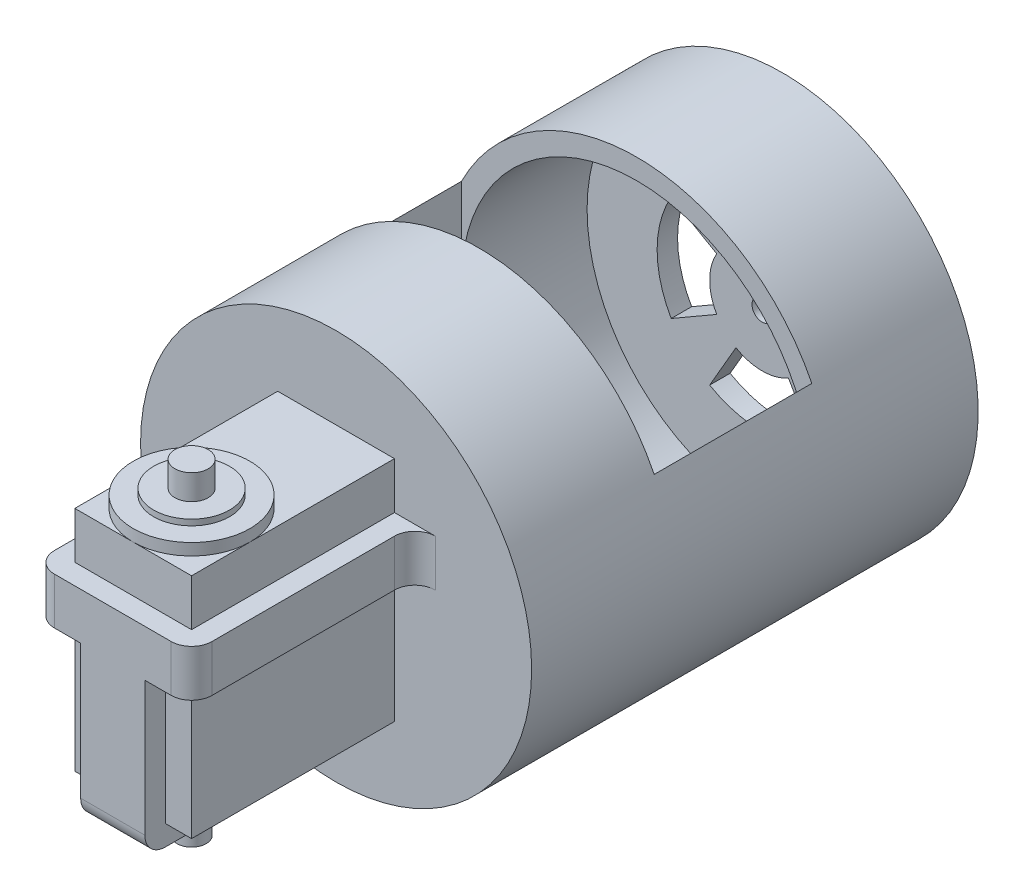
SolidWorks part; units mm, degrees
ref_plane "Front Plane" through (0, 0, 0) normal (0, 0, 1) x (1, 0, 0)
ref_plane "Top Plane" through (0, 0, 0) normal (0, 1, 0) x (1, 0, 0)
ref_plane "Right Plane" through (0, 0, 0) normal (1, 0, 0) x (0, 0, -1)
sketch "Sketch1" plane through (0, 0, 0) normal (0, 0, 1) x (1, 0, 0)
  circle A1 centre (0, 0) radius 33.5
extrude "Boss-Extrude3" add sketch "Sketch1" along normal blind 16.5 contours A1
sketch "Sketch2" plane through (0, 0, 16.5) normal (0, 0, 1) x (1, 0, 0)
  line L0 (0, 0) -> (33.5, 0) construction
  line L1 (-10, 19.5) -> (10, 19.5)
  line L2 (-10, 19.5) -> (-10, -19.5)
  line L3 (-10, -19.5) -> (10, -19.5)
  line L4 (10, 19.5) -> (10, -19.5)
  line L5 (0, 0) -> (0, -33.5) construction
  circle A0 centre (0, 0) radius 33.5 construction
  dimension "D1" = 10
  dimension "D2" = 19.5
extrude "Boss-Extrude4" add sketch "Sketch2" along normal blind 34.758
sketch "Sketch3" plane through (0, 19.5, 0) normal (0, 1, 0) x (1, 0, 0)
  circle A0 centre (0, -41.258) radius 10
  circle A1 centre (0, -41.258) radius 6.5
  circle A2 centre (0, -41.258) radius 2.85
extrude "Boss-Extrude5" add sketch "Sketch3" along normal blind 2 contours A0 A1 region at (-9.7172, 19.5, 41.258)
extrude "Boss-Extrude6" add sketch "Sketch3<3>" along normal blind 3 contours A1
sketch "Sketch3<3>" plane through (0, 19.5, 0) normal (0, 1, 0) x (1, 0, 0) same geometry as "Sketch3"
extrude "Boss-Extrude7" add sketch "Sketch3<4>" along normal blind 7.3 contours A2
sketch "Sketch3<4>" plane through (0, 19.5, 0) normal (0, 1, 0) x (1, 0, 0) same geometry as "Sketch3"
sketch "Sketch5" plane through (0, 0, 51.258) normal (0, 0, 1) x (1, 0, 0)
  line L0 (-10, -19.5) -> (10, -19.5) construction
  line L1 (-5.5, -23) -> (5.5, -23)
  line L2 (-5.5, -23) -> (-5.5, -19.5)
  line L3 (-5.5, -19.5) -> (5.5, -19.5)
  line L4 (5.5, -23) -> (5.5, -19.5)
  line L5 (10, -19.5) -> (10, 19.5) construction
  line L6 (10, 11.5) -> (13.5, 11.5)
  line L7 (10, 11.5) -> (10, 3.5)
  line L8 (10, 3.5) -> (13.5, 3.5)
  line L9 (13.5, 11.5) -> (13.5, 3.5)
  line L10 (-10, 19.5) -> (-10, -19.5) construction
  line L11 (-10, 11.5) -> (-13.5, 11.5)
  line L12 (-10, 11.5) -> (-10, 3.5)
  line L13 (-10, 3.5) -> (-13.5, 3.5)
  line L14 (-13.5, 11.5) -> (-13.5, 3.5)
  line L15 (-10, -19.5) -> (10, -19.5) construction
  point P19 (0, 0)
  point P20 (0, 0)
  point P21 (-11.75, 3.5)
  dimension "D1" = 5.5
  dimension "D2" = 23
  dimension "D3" = 23
  dimension "D4" = 8
  dimension "D5" = 8
  dimension "D6" = 3.5
  dimension "D7" = 3.5
extrude "Boss-Extrude8" add sketch "Sketch5" against normal up to surface (34.758 mm away) up to face at (0, 0, 16.5)
sketch "Sketch6" plane through (0, 0, 51.258) normal (0, 0, 1) x (1, 0, 0)
  line L1 (-13.5, 11.5) -> (13.5, 11.5)
  line L2 (-13.5, 11.5) -> (-13.5, 3.5)
  line L3 (-13.5, 3.5) -> (13.5, 3.5)
  line L4 (13.5, 11.5) -> (13.5, 3.5)
  line L5 (5.5, -23) -> (-5.5, -23)
  line L6 (5.5, -23) -> (5.5, 11.5)
  line L7 (5.5, 11.5) -> (-5.5, 11.5)
  line L8 (-5.5, -23) -> (-5.5, 11.5)
  point P11 (-5.5, -23)
  line M6 (-10, 11.5) -> (-13.5, 11.5)
  line M7 (-13.5, 11.5) -> (-13.5, 3.5)
  line M8 (-13.5, 3.5) -> (-10, 3.5)
  line M11 (-5.5, -19.5) -> (-5.5, -23)
  line M12 (-5.5, -23) -> (5.5, -23)
  line M13 (5.5, -23) -> (5.5, -19.5)
  line M16 (10, 3.5) -> (13.5, 3.5)
  line M17 (13.5, 3.5) -> (13.5, 11.5)
  line M18 (13.5, 11.5) -> (10, 11.5)
extrude "Boss-Extrude9" add sketch "Sketch6" along normal blind 3.5 contours L8 L3 L6 L1 | L6 L3 L1 M16 M17 M18 | L8 L6 L3 M11 M12 M13 | L3 L8 L1 M6 M7 M8 region at (-9.5, 7.5, 51.258) region at (0, 7.5, 51.258) region at (9.5, 7.5, 51.258) region at (0, -9.75, 51.258)
sketch "Sketch7" plane through (0, -23, 0) normal (0, -1, 0) x (1, 0, 0)
  circle A0 centre (0, 41.258) radius 2.5
extrude "Boss-Extrude10" add sketch "Sketch7" along normal blind 6 contours A0
fillet "Fillet1" radius 3.5 2 edges at (-13.5, 7.5, 54.758) (13.5, 7.5, 54.758)
fillet "Fillet2" radius 3.5 1 edges at (0, -23, 54.758)
fillet "Fillet3" radius 3.5 1 edges at (13.5, 7.5, 16.5)
fillet "Fillet4" radius 3.5 1 edges at (-13.5, 7.5, 16.5)
sketch "Sketch14" plane through (0, 0, 0) normal (0, 0, -1) x (-1, 0, 0)
  line L0 (0, 0) -> (0, 18) construction
  line L1 (0, 0) -> (9, 15.5885)
  line L2 (0, 0) -> (-9, 15.5885)
  circle A0 centre (0, 0) radius 1.25
  circle A1 centre (0, 0) radius 9
  circle A2 centre (0, 0) radius 18
  dimension "D1" = 60
  dimension "D2" = 30
extrude "Cut-Extrude11" cut sketch "Sketch14" against normal blind 3.5 contours L0 A1 L1 A2 | A1 L0 A2 L2 region at (3.5822, 13.369, 0) region at (-3.5822, 13.369, 0)
pattern_circular "CirPattern4" count 4 over 360 about axis through (0, 0, 0) along (0, 0, 1) of "Cut-Extrude11"
extrude "Cut-Extrude12" cut sketch "Sketch14<3>" against normal blind 3.5 contours A0
sketch "Sketch14<3>" plane through (0, 0, 0) normal (0, 0, -1) x (-1, 0, 0) same geometry as "Sketch14"
sketch "Sketch16" plane through (0, 0, 0) normal (0, 0, -1) x (-1, 0, 0)
  circle A0 centre (0, 0) radius 33.5
  circle A1 centre (0, 0) radius 30
extrude "Boss-Extrude15" add sketch "Sketch16" along normal blind 60 contours A0 | A1
ref_plane "Plane4" through (0, 33.5, 0) normal (0, 1, 0) x (1, 0, 0)
sketch "Sketch17" plane through (0, 33.5, 0) normal (0, 1, 0) x (1, 0, 0)
  line L0 (33.5, 60) -> (-33.5, 60) construction
  line L1 (-30, 35) -> (30, 35)
  line L2 (-30, 35) -> (-30, 8)
  line L3 (-30, 8) -> (30, 8)
  line L4 (30, 35) -> (30, 8)
  dimension "D1" = 25
  dimension "D2" = 27
  dimension "D3" = 60
  dimension "D4" = 30
extrude "Cut-Extrude13" cut sketch "Sketch17" against normal blind 33.5 contours L2 L3 L4 L1
sketch "Sketch18" plane through (0, 0, -60) normal (0, 0, -1) x (-1, 0, 0)
  line L0 (0, 0) -> (0, 18) construction
  line L1 (0, 0) -> (-9, 15.5885)
  line L2 (0, 0) -> (9, 15.5885)
  circle A0 centre (0, 0) radius 33.5
  circle A1 centre (0, 0) radius 1.75
  circle A2 centre (0, 0) radius 9
  circle A3 centre (0, 0) radius 18
  dimension "D1" = 60
  dimension "D2" = 30
extrude "Boss-Extrude16" add sketch "Sketch18" against normal blind 3.5 contours A0
extrude "Cut-Extrude14" cut sketch "Sketch18<3>" against normal blind 3.5 contours A2 L0 A3 L1 | L0 A2 L2 A3 region at (3.5822, 13.369, -60) region at (-3.5822, 13.369, -60)
sketch "Sketch18<3>" plane through (0, 0, -60) normal (0, 0, -1) x (-1, 0, 0) same geometry as "Sketch18"
pattern_circular "CirPattern5" count 4 over 360 about axis through (0, 0, 16.5) along (0, 0, -1) of "Cut-Extrude14" reverse direction yes
extrude "Cut-Extrude15" cut sketch "Sketch18<4>" against normal blind 3.5 contours L0 L2 A1 | L1 L0 A1 | L1 A1 L2 region at (0.2985, 1.1141, -60) region at (0, -0.2228, -60) region at (-0.2985, 1.1141, -60)
sketch "Sketch18<4>" plane through (0, 0, -60) normal (0, 0, -1) x (-1, 0, 0) same geometry as "Sketch18"
ref_plane "Plane5" through (0, 0, 0) normal (0, 1, 0) x (1, 0, 0)
sketch "Sketch20" plane through (0, 0, 0) normal (0, 1, 0) x (1, 0, 0)
  circle A0 centre (0, -41.258) radius 1.5
